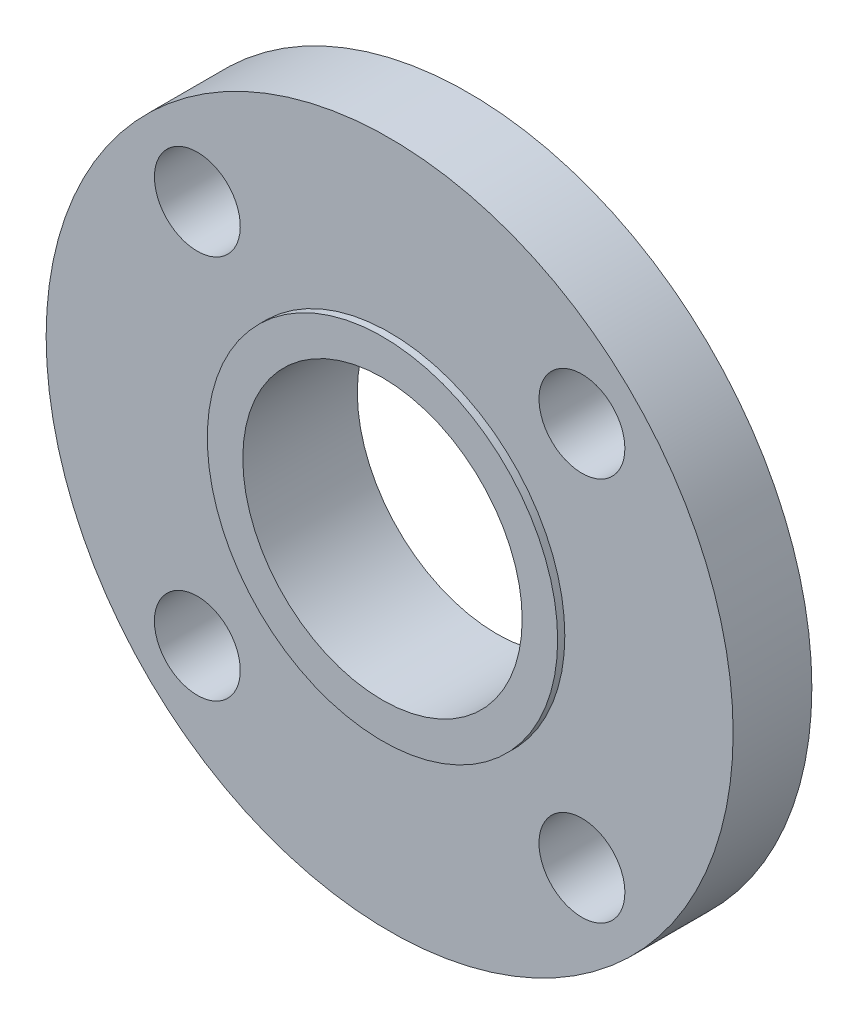
SolidWorks part; units mm, degrees
ref_plane "front" through (0, 0, 0) normal (0, 0, 1) x (1, 0, 0)
ref_plane "top" through (0, 0, 0) normal (0, 1, 0) x (1, 0, 0)
ref_plane "side" through (0, 0, 0) normal (1, 0, 0) x (0, 0, -1)
sketch "Hub Diameter" plane through (0, 0, 0) normal (0, 0, 1) x (1, 0, 0)
  circle A0 centre (0, 0) radius 38.862
  dimension "Diameter of Hub X" = 77.724
extrude "Hub" add sketch "Hub Diameter" against normal blind 25.4
ref_plane "Flange starting plane" through (0, 0, -1.5875) normal (0, 0, 1) x (1, 0, 0)
ref_plane "Flange end plane" through (0, 0, -19.05) normal (0, 0, 1) x (1, 0, 0)
sketch "Flange Diameter" plane through (0, 0, -1.5875) normal (0, 0, 1) x (1, 0, 0)
  circle A0 centre (0, 0) radius 76.2
  dimension "Outside Diameter of Flange O" = 152.4
extrude "Flange" add sketch "Flange Diameter" against normal up to surface (17.4625 mm away) up to plane "Flange end plane"
ref_axis "Axis of Revolution for Bore" through (0, 0, -50) along (0, 0, 1)
sketch "Bolt Diameter" plane through (0, 0, -1.5875) normal (0, 0, 1) x (1, 0, 0)
  line L0 (0, 19.05) -> (0, -19.05) construction
  line L1 (17.2244, 17.2244) -> (-17.2244, -17.2244) construction
  circle A0 centre (42.6562, 42.6562) radius 9.525
  circle A1 centre (0, 0) radius 60.325 construction
  point P0 (0, 0)
  dimension "Diameter of Bolt Holes" = 19.05
  dimension "Diameter of Bolt Circle" = 120.65
  dimension "Angle" = 45
sketch "Revolution profile for Bore" plane through (0, 0, 0) normal (0, 1, 0) x (1, 0, 0)
  line L0 (0, -19.5213) -> (0, 228.6) construction
  line L1 (0, 1.5875) -> (0, 0) construction
  line L2 (0, 0) -> (30.988, 0)
  line L3 (30.988, 0) -> (30.988, 228.6)
  line L4 (30.988, 228.6) -> (0, 228.6)
  line L5 (0, 228.6) -> (0, 0)
  point P4 (0, 0)
  dimension "D2" = 61.976
  dimension "Hub Length Y" = 228.6
revolve "Bore" cut sketch "Revolution profile for Bore" angle 360 about L0
extrude "Bolt Hole" cut sketch "Bolt Diameter" against normal through all
pattern_circular "Bolt Hole Pattern" count 4 every 90 about axis through (0, 0, -50) along (0, 0, 1) of "Bolt Hole"
sketch "Sketch1" plane through (0, 0, 0) normal (0, 1, 0) x (1, 0, 0)
  line L1 (0, -19.5213) -> (0, 228.6) construction
  line L2 (-30.988, 0) -> (30.988, 0) construction
  point P0 (0, 6.35)
  point P6 (0, 0)
  dimension "D1" = 6.35
other "CPoint1" parameters "Diameter"=50.8, "StubLength"=0
ref_axis "Axis1" through (0, 0, -16.35) along (0, 0, 1)
other "RPoint1"
ref_axis "Axis of Rotation" through (0, 0, -25.4) along (0, 0, 1)
ref_axis "Vertical" through (0, 0, -6.35) along (0, 1, 0)
equation "\"flange height@Flange starting plane\" =  ( \"Hub Length Y@Hub\" - \"Thickness of Flange C@Flange end plane\" )  / 3"
equation "\"angular position of Bolt Holes@Bolt Hole Pattern\" = 360/\"Number of Bolt Holes@Bolt Hole Pattern\""
